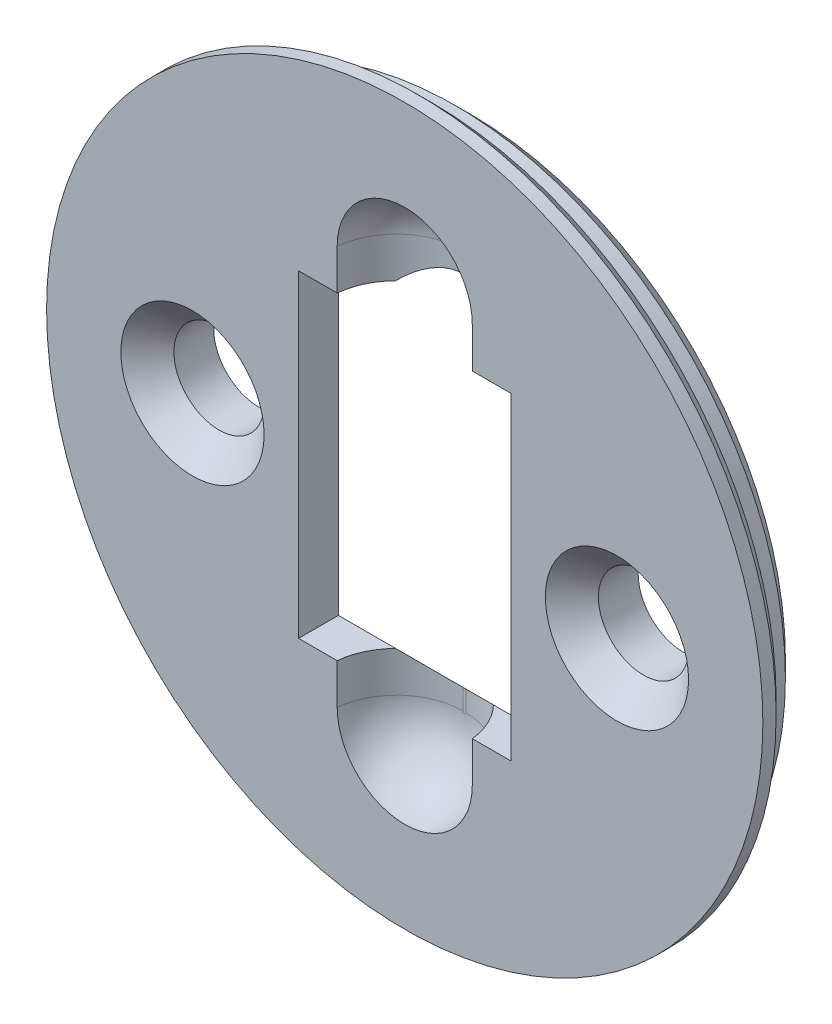
SolidWorks part; units mm, degrees
ref_plane "Front Plane" through (0, 0, 0) normal (0, 0, 1) x (1, 0, 0)
ref_plane "Top Plane" through (0, 0, 0) normal (0, 1, 0) x (1, 0, 0)
ref_plane "Right Plane" through (0, 0, 0) normal (1, 0, 0) x (0, 0, -1)
sketch "Sketch1" plane through (0, 0, 0) normal (0, 0, 1) x (1, 0, 0)
  line L0 (0, 9.3188) -> (0, -6.9028) construction
  circle A0 centre (0, 0) radius 12.45
  circle A1 centre (-8, 0) radius 1.7
  circle A2 centre (8, 0) radius 1.7
  dimension "D2" = 24.9
  dimension "D3" = 3.4
  dimension "D1" = 16
extrude "Boss-Extrude1" add sketch "Sketch1" against normal blind 1.5
sketch "Sketch2" plane through (0, 0, -1.5) normal (0, 0, -1) x (-1, 0, 0)
  line L1 (-4, 6) -> (4, 6)
  line L2 (-4, 6) -> (-4, -6)
  line L3 (-4, -6) -> (4, -6)
  line L4 (4, 6) -> (4, -6)
  line L5 (-4, 6) -> (4, -6) construction
  line L6 (-4, -6) -> (4, 6) construction
  point P0 (0, 0)
  dimension "D1" = 12
  dimension "D2" = 8
sketch "Sketch3" plane through (0, 0, 0) normal (0, 0, 1) x (1, 0, 0)
  circle A0 centre (0, 0) radius 13.5
  circle A1 centre (-8, 0) radius 1.7
  circle A2 centre (8, 0) radius 1.7
  circle A3 centre (-8, 0) radius 1.7 construction
  dimension "D1" = 27
extrude "Boss-Extrude3" add sketch "Sketch3" along normal blind 1
chamfer "Chamfer2" distance 0.5 angle 45 1 edges at (13.5, 0, 0)
sketch "Sketch4" plane through (0, 0, 1) normal (0, 0, 1) x (1, 0, 0)
  line L0 (0, 7.5257) -> (0, -7.5257) construction
  line L1 (2.5463, 7.5257) -> (2.5463, -7.5257)
  line L2 (-2.5463, 7.5257) -> (-2.5463, -7.5257)
  arc A0 (2.5463, 7.5257) -> (-2.5463, 7.5257) centre (0, 7.5257) ccw
  arc A1 (-2.5463, -7.5257) -> (2.5463, -7.5257) centre (0, -7.5257) ccw
  point P2 (0, 0)
extrude "Cut-Extrude1" cut sketch "Sketch4" against normal blind 2.25
fillet "Fillet1" radius 2.5 4 edges at (-2.5463, 0, -1.25) (2.5463, 0, -1.25) (0, 10.0719, -1.25) (0, -10.0719, -1.25)
chamfer "Chamfer3" distance 1 angle 45 2 edges at (9.7, 0, 1) (-6.3, 0, 1)
extrude "Cut-Extrude2" cut sketch "Sketch2" against normal through all
chamfer "Chamfer4" distance 1 angle 45 4 edges at (0, 6, -1.5) (4, 0, -1.5) (0, -6, -1.5) (-4, 0, -1.5)
chamfer "Chamfer5" distance 0.6 angle 45 1 edges at (12.45, 0, -1.5)
